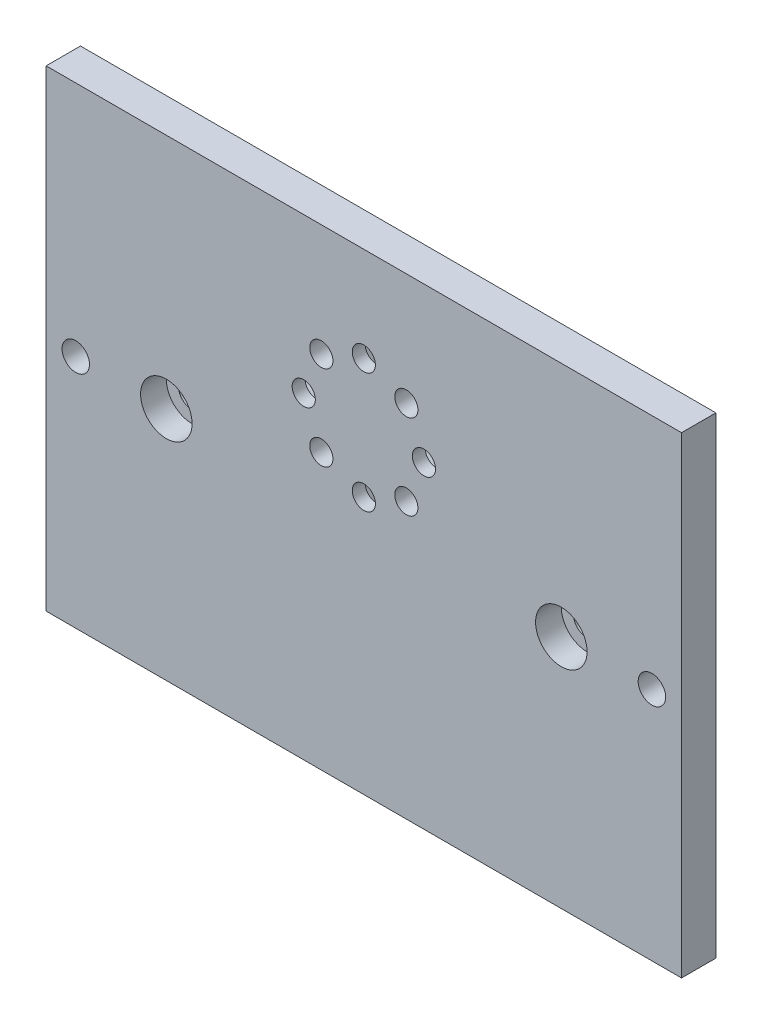
SolidWorks part; units mm, degrees
ref_plane "前基準面" through (0, 0, 0) normal (0, 0, 1) x (1, 0, 0)
ref_plane "上基準面" through (0, 0, 0) normal (0, 1, 0) x (1, 0, 0)
ref_plane "右基準面" through (0, 0, 0) normal (1, 0, 0) x (0, 0, -1)
sketch "草圖1" plane through (0, 0, 0) normal (0, 0, 1) x (1, 0, 0)
  line L1 (-37, 27.5) -> (37, 27.5)
  line L2 (-37, 27.5) -> (-37, -27.5)
  line L3 (-37, -27.5) -> (37, -27.5)
  line L4 (37, 27.5) -> (37, -27.5)
  line L5 (-37, 27.5) -> (37, -27.5) construction
  line L6 (-37, -27.5) -> (37, 27.5) construction
  point P0 (0, 0)
  dimension "D1" = 74
  dimension "D2" = 55
extrude "填料-伸長1" add sketch "草圖1" along normal blind 4
sketch "草圖2" plane through (0, 0, 4) normal (0, 0, 1) x (1, 0, 0)
  line L0 (-33.55, -0.1) -> (33.55, -0.1) construction
  line L1 (-37, 9.5) -> (37, 9.5) construction
  line L4 (0, 27.5) -> (0, -27.5) construction
  line L5 (37, 27.5) -> (-37, 27.5) construction
  line L6 (-37, -27.5) -> (37, -27.5) construction
  line L7 (37, -27.5) -> (37, 27.5) construction
  line L8 (-37, 27.5) -> (-37, -27.5) construction
  circle A0 centre (-33.55, -0.1) radius 1.6
  circle A1 centre (33.55, -0.1) radius 1.6
  circle A2 centre (-23, -0.1) radius 1.6
  circle A3 centre (23, -0.1) radius 1.6
  circle A4 centre (0, 2.5) radius 1.35
  circle A5 centre (-4.9497, 4.5503) radius 1.35
  circle A6 centre (-7, 9.5) radius 1.35
  circle A7 centre (-4.9497, 14.4497) radius 1.35
  circle A8 centre (0, 16.5) radius 1.35
  circle A9 centre (4.9497, 14.4497) radius 1.35
  circle A10 centre (7, 9.5) radius 1.35
  circle A11 centre (4.9497, 4.5503) radius 1.35
  point P8 (0, -0.1)
  point P40 (0, 9.5)
  point P43 (0, 9.5)
  dimension "D3" = 3.2
  dimension "D7" = 2.7
  dimension "D1" = 67.1
  dimension "D2" = 46
  dimension "D4" = 23
  dimension "D5" = 27.4
  dimension "D6" = 7
  dimension "D9" = 37
  dimension "D8" = 8
extrude "除料-伸長1" cut sketch "草圖2" against normal through all contours A0 | A2 | A3 | A1
extrude "除料-伸長2" cut sketch "草圖2<3>" against normal through all contours A4 | A11 | A10 | A9 | A7 | A6 | A5 | A8 region at (0, 2.5, 4) region at (-4.9497, 4.5503, 4) region at (-7, 9.5, 4) region at (-4.9497, 14.4497, 4) region at (4.9497, 14.4497, 4) region at (7, 9.5, 4) region at (4.9497, 4.5503, 4)
sketch "草圖2<3>" plane through (0, 0, 4) normal (0, 0, 1) x (1, 0, 0) same geometry as "草圖2"
sketch "草圖3" plane through (0, 0, 0) normal (0, 0, -1) x (-1, 0, 0)
  line L6 (-1.5877, 19.25) -> (1.5877, 19.25)
  line L7 (1.5877, 19.25) -> (3.1754, 16.5)
  line L8 (3.1754, 16.5) -> (1.5877, 13.75)
  line L9 (1.5877, 13.75) -> (-1.5877, 13.75)
  line L10 (-1.5877, 13.75) -> (-3.1754, 16.5)
  line L11 (-3.1754, 16.5) -> (-1.5877, 19.25)
  line L12 (0, 16.5) -> (0, 9.5) construction
  line L13 (9.75, 7.9123) -> (7, 6.3246)
  line L14 (7, 6.3246) -> (4.25, 7.9123)
  line L15 (4.25, 7.9123) -> (4.25, 11.0877)
  line L16 (4.25, 11.0877) -> (7, 12.6754)
  line L17 (7, 12.6754) -> (9.75, 11.0877)
  line L18 (9.75, 11.0877) -> (9.75, 7.9123)
  line L19 (-1.5877, -0.25) -> (-3.1754, 2.5)
  line L20 (-3.1754, 2.5) -> (-1.5877, 5.25)
  line L21 (-1.5877, 5.25) -> (1.5877, 5.25)
  line L22 (1.5877, 5.25) -> (3.1754, 2.5)
  line L23 (3.1754, 2.5) -> (1.5877, -0.25)
  line L24 (1.5877, -0.25) -> (-1.5877, -0.25)
  line L25 (-9.75, 11.0877) -> (-7, 12.6754)
  line L26 (-7, 12.6754) -> (-4.25, 11.0877)
  line L27 (-4.25, 11.0877) -> (-4.25, 7.9123)
  line L28 (-4.25, 7.9123) -> (-7, 6.3246)
  line L29 (-7, 6.3246) -> (-9.75, 7.9123)
  line L30 (-9.75, 7.9123) -> (-9.75, 11.0877)
  circle A0 centre (0, 16.5) radius 3.1754 construction
  point P0 (0, 16.5)
  point P5 (0, 0)
  point P11 (0, 9.5)
  point P32 (0, 9.5)
  dimension "D1" = 5.5
  dimension "D2" = 7
  dimension "D3" = 4
extrude "除料-伸長3" cut sketch "草圖3" against normal blind 2.5
sketch "草圖5" plane through (0, 0, 4) normal (0, 0, 1) x (1, 0, 0)
  circle A0 centre (23, -0.1) radius 3
  circle A1 centre (-23, -0.1) radius 3
  dimension "D1" = 6
extrude "除料-伸長4" cut sketch "草圖5" against normal blind 3
